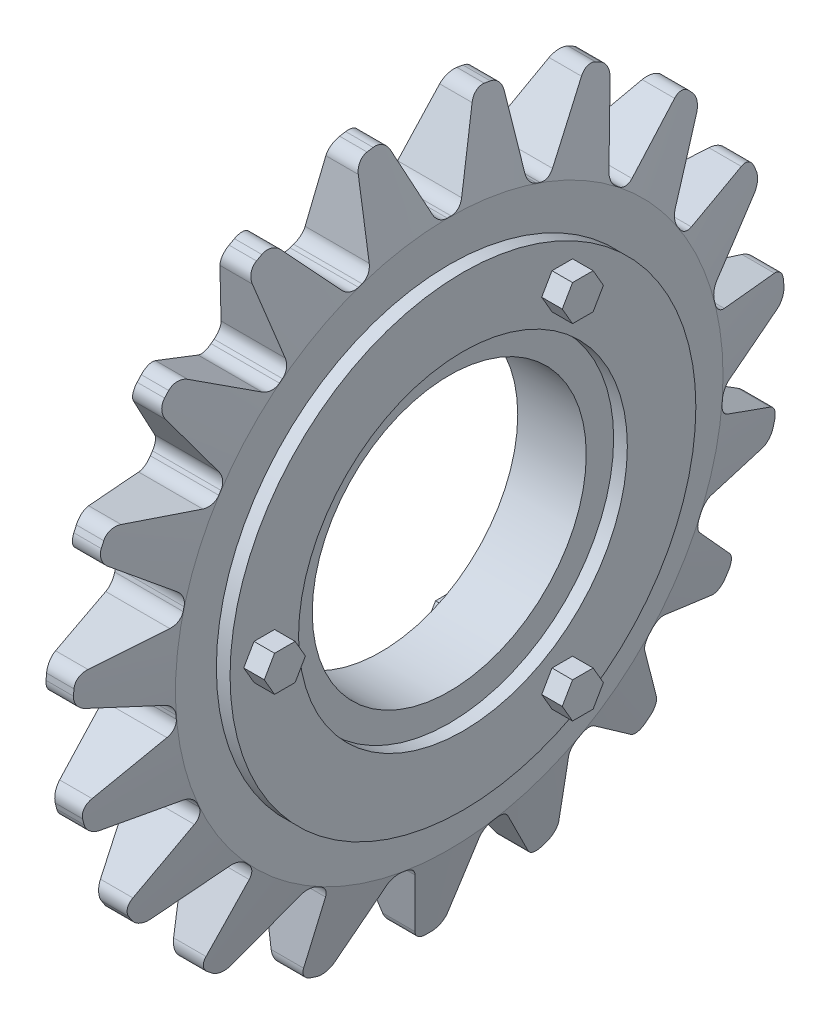
SolidWorks part; units mm, degrees
material "AISI 8620 Steel, carburized"
ref_plane "Front Plane" through (0, 0, 0) normal (1, 0, 0) x (0, 1, 0)
ref_plane "Top Plane" through (0, 0, 0) normal (0, 0, 1) x (0, 1, 0)
ref_plane "Right Plane" through (0, 0, 0) normal (0, 1, 0) x (-1, 0, 0)
sketch "Sketch1" plane through (0, 0, 0) normal (1, 0, 0) x (0, 1, 0)
  circle A0 centre (0, 0) radius 20
  circle A1 centre (0, 0) radius 17
  circle A2 centre (0, 0) radius 12
  circle A3 centre (0, 0) radius 10
  dimension "D1" = 24
  dimension "D2" = 34
  dimension "D3" = 40
  dimension "D4" = 20
extrude "Boss-Extrude1" add sketch "Sketch1" along normal mid plane 5 contours A0 A1 | A1 A2 | A2 A3 region at (0, -19.4343, 0) region at (0, -16.5192, 0) region at (0, -11.6606, 0)
sketch "Sketch2" plane through (2.5, 0, 0) normal (1, 0, 0) x (0, 1, 0)
  line L0 (0, 0) -> (-50.1268, 0) construction
  line L1 (-26, 1) -> (-26, -1)
  line L2 (-26, -1) -> (-19.8431, -2.5)
  line L3 (-26, 1) -> (-19.8431, 2.5)
  circle A0 centre (0, 0) radius 20 construction
  arc A1 (-19.8431, 2.5) -> (-19.8431, -2.5) centre (0, 0) ccw
  arc A2 (-25.9806, 1.0047) -> (-25.9806, -1.0047) centre (0, 0) ccw
  circle A4 centre (0, 0) radius 26 construction
  circle A5 centre (0, 0) radius 20 construction
  point P8 (-26, 0)
  point P10 (31.5581, 9.6483)
  point P15 (19.1261, 5.8474)
  circle M6 centre (0, 0) radius 20
  dimension "D3" = 5
  dimension "D2" = 2
  dimension "D1" = 6
extrude "Boss-Extrude2" add sketch "Sketch2" against normal up to surface (5 mm away) contours L3 A2 L2 M6 region at (2.5, -22.5438, 0) up to face at (-2.5, 0, -20)
fillet "Fillet1" radius 1 2 edges at (0, -25.9806, -1.0047) (0, -25.9806, 1.0047)
fillet "Fillet2" radius 1 2 edges at (0, -19.8431, -2.5) (0, -19.8431, 2.5)
pattern_circular "CirPattern1" count 19 over 360 about axis through (2.5, 0, 0) along (1, 0, 0) of "Fillet1", "Boss-Extrude2", "Fillet2"
sketch "Sketch7" plane through (2.5, 0, 0) normal (1, 0, 0) x (0, 1, 0)
  line L2 (-36.3144, 0) -> (37.4583, 0) construction
  circle A1 centre (0, 0) radius 33
  dimension "D1" = 66
ref_plane "Plane1" through (0, 0, 0) normal (0, 0, -1) x (0, 1, 0)
sketch "Sketch3" plane through (0, 0, 0) normal (0, 0, 1) x (-1, 0, 0)
  line L3 (-14.363, 0) -> (11.8314, 0) construction
  line L4 (0, 37.2459) -> (0, -38.8612) construction
  line L6 (1, 26) -> (2.5, 26)
  line L12 (1, 26) -> (2.5, 19.9838)
  line L14 (2.5, 26) -> (-2.5, 26)
  line L16 (2.5, 26) -> (2.5, 19.9838)
  line L19 (2.5, 26) -> (-2.5, 26)
  line L21 (-2.5, 26) -> (-2.5, 10)
  line L22 (-2.5, -10) -> (-2.5, -20)
  line L23 (-2.5, -10) -> (-2.5, -20)
  line L24 (-2.5, 26) -> (-2.5, 10)
  line L30 (-2.5, 26) -> (-2.5, 19.9838)
  line L31 (-1, 26) -> (-2.5, 26)
  line L32 (-1, 26) -> (-2.5, 19.9838)
  dimension "D1" = 1
  dimension "D2" = 256
revolve "Cut-Revolve1" cut sketch "Sketch3" angle 360 about L3 region at (-2, -23.9946, 0) region at (2, -23.9946, 0)
extrude "Boss-Extrude3" add sketch "Sketch1<3>" against normal mid plane 7 contours A1 A2 region at (0, -16.5192, 0)
sketch "Sketch1<3>" plane through (0, 0, 0) normal (1, 0, 0) x (0, 1, 0) same geometry as "Sketch1"
sketch "Sketch6" plane through (-3.5, 0, 0) normal (-1, 0, 0) x (0, -1, 0)
  line L0 (0, 0) -> (0, 33.6066) construction
  line L1 (0, 12.9989) -> (1.3, 13.7494)
  line L2 (1.3, 13.7494) -> (1.3, 15.2506)
  line L3 (1.3, 15.2506) -> (0, 16.0011)
  line L4 (0, 16.0011) -> (-1.3, 15.2506)
  line L5 (-1.3, 15.2506) -> (-1.3, 13.7494)
  line L6 (-1.3, 13.7494) -> (0, 12.9989)
  circle A0 centre (0, 14.5) radius 1.3 construction
  circle A1 centre (0, 0) radius 17 construction
  circle A6 centre (0, 0) radius 14.5
  dimension "D1" = 2.5
  dimension "D2" = 2.6
extrude "Boss-Extrude4" add sketch "Sketch6" along normal blind 1.5 contours A6 L2 L3 L4 L5 | L2 A6 L5 L6 L1 region at (-3.5, 0, 13.9063) region at (-3.5, 0, 15.0736)
pattern_circular "CirPattern3" count 3 over 360 about axis through (-3.5, 0, 0) along (1, 0, 0) of "Boss-Extrude4"
mirror "Mirror1" about plane through (0, 0, 0) normal (1, 0, 0) of "CirPattern3", "Boss-Extrude4"
ref_axis "Axis1" through (2.5, 0, 0) along (-1, 0, 0)
